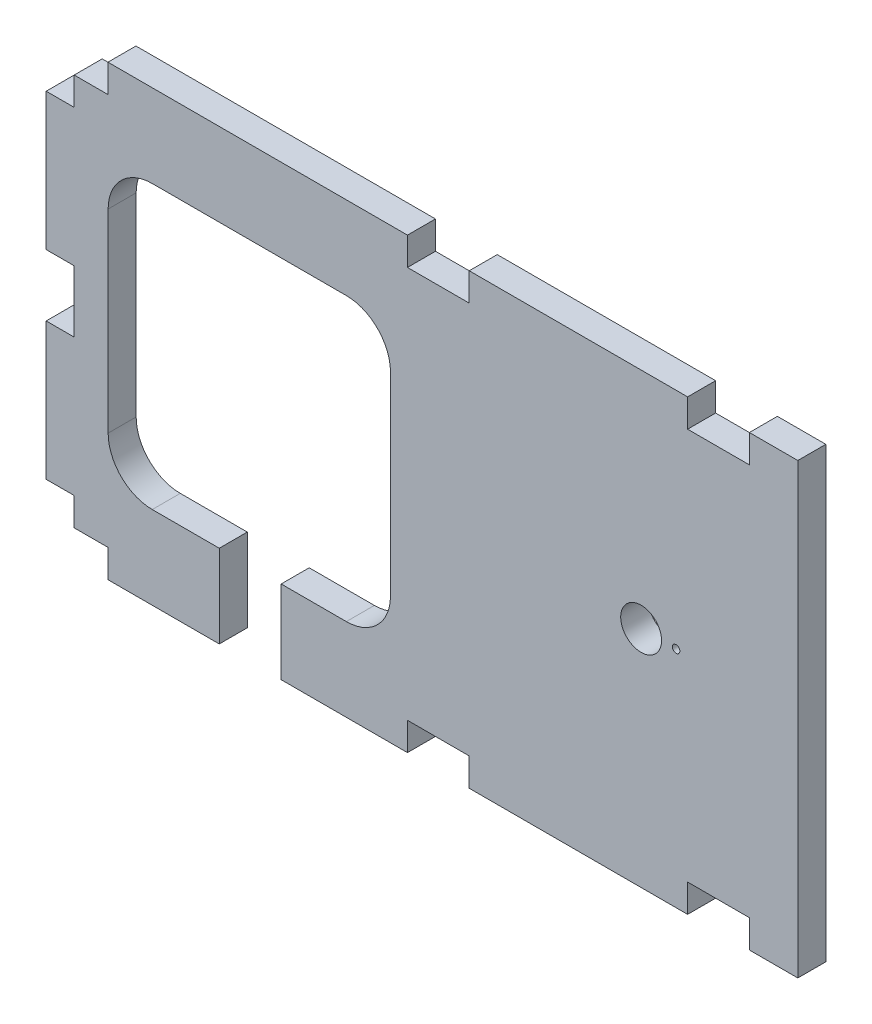
SolidWorks part; units mm, degrees
ref_plane "Front Plane" through (0, 0, 0) normal (0, 0, 1) x (1, 0, 0)
ref_plane "Top Plane" through (0, 0, 0) normal (0, 1, 0) x (1, 0, 0)
ref_plane "Right Plane" through (0, 0, 0) normal (1, 0, 0) x (0, 0, -1)
sketch "Sketch2" plane through (0, 0, 0) normal (0, 0, 1) x (1, 0, 0)
  line L1 (-88.9, -50.8) -> (88.9, -50.8)
  line L2 (-88.9, -50.8) -> (-88.9, 50.8)
  line L3 (-88.9, 50.8) -> (88.9, 50.8)
  line L4 (88.9, -50.8) -> (88.9, 50.8)
  line L5 (-88.9, -50.8) -> (88.9, 50.8) construction
  line L6 (-88.9, 50.8) -> (88.9, -50.8) construction
  point P0 (0, 0)
  dimension "D1" = 101.6
  dimension "D2" = 177.8
extrude "Boss-Extrude3" add sketch "Sketch2" along normal blind 6.35
sketch "Sketch3" plane through (0, 0, 6.35) normal (0, 0, 1) x (1, 0, 0)
  line L0 (-88.9, 0) -> (0, 0) construction
  line L1 (-88.9, 50.8) -> (-88.9, -50.8) construction
  line L2 (0, 0) -> (88.9, 0) construction
  line L3 (88.9, -50.8) -> (88.9, 50.8) construction
  line L4 (0, 50.8) -> (0, -50.8) construction
  line L5 (88.9, 50.8) -> (-88.9, 50.8) construction
  line L6 (-88.9, -50.8) -> (88.9, -50.8) construction
  line L7 (-9.4121, 0) -> (-42.6438, 0) construction
  line L8 (45.9739, 0) -> (-9.4121, 0) construction
  line L9 (-10.8508, 32) -> (-10.8508, 0)
  line L10 (-10.8508, -32) -> (-74.8508, -32)
  line L11 (-74.8508, -32) -> (-74.8508, 32)
  line L12 (-74.8508, 32) -> (-42.8508, 32)
  line L13 (-49.6596, -32) -> (-49.6596, -50.8)
  line L14 (-10.8508, 0) -> (-10.8508, -32)
  line L15 (-42.8508, 32) -> (-10.8508, 32)
  line L16 (-42.8508, 50.8) -> (-42.6438, 0) construction
  line L20 (-35.6279, -32) -> (-35.6279, -50.8)
  line L26 (-35.6279, -50.8) -> (-49.6596, -50.8)
  line L29 (26.7151, -50.8) -> (26.7151, 50.8) construction
  line L30 (-66.2169, 23.5732) -> (-66.2169, 28.0633) construction
  circle A7 centre (45.9739, 0) radius 4.635
  line M4 (-88.9, -50.8) -> (88.9, -50.8)
  dimension "D1" = 32
  dimension "D2" = 32
  dimension "D3" = 32
  dimension "D8" = 9.27
  dimension "D5" = 55.386
extrude "Cut-Extrude1" cut sketch "Sketch3" against normal through all contours L10 | L11 | L20 L10 L13 M4 | A7 region at (-42.8508, 0, 6.35) region at (-42.6438, -41.4, 6.35)
sketch "Sketch7" plane through (0, 0, 6.35) normal (0, 0, 1) x (1, 0, 0)
  line L1 (88.9, 50.8) -> (-88.9, 50.8) construction
  line L2 (-88.9, 50.8) -> (-88.9, -50.8) construction
  line L3 (-88.9, 50.8) -> (-88.9, -50.8) construction
  line L4 (-88.9, -7) -> (-88.9, 7)
  line L5 (-88.9, 50.8) -> (-74.9, 50.8)
  line L6 (-88.9, 50.8) -> (-88.9, 44.45)
  line L7 (-74.9, 44.45) -> (-82.55, 44.45)
  line L8 (-74.9, 50.8) -> (-74.9, 44.45)
  line L9 (-88.9, -50.8) -> (-74.9, -50.8)
  line L10 (-88.9, -50.8) -> (-88.9, -44.45)
  line L11 (-74.9, -44.45) -> (-82.55, -44.45)
  line L12 (-74.9, -50.8) -> (-74.9, -44.45)
  line L13 (-88.9, -7) -> (-82.55, -7)
  line L14 (-88.9, 7) -> (-82.55, 7)
  line L15 (-82.55, -7) -> (-82.55, 7)
  line L16 (88.9, -50.8) -> (88.9, 50.8) construction
  line L17 (7, 44.45) -> (-88.9, 44.45)
  line L18 (7, 44.45) -> (7, 50.8)
  line L19 (-7, 50.8) -> (7, 50.8)
  line L20 (-88.9, 44.45) -> (-88.9, 50.8)
  line L21 (70.509, 50.8) -> (70.509, 44.45)
  line L22 (-7, -32) -> (-7, 50.8) construction
  line L23 (7, -50.8) -> (56.509, -50.8)
  line L24 (56.509, -50.8) -> (70.509, -50.8)
  line L25 (56.509, -50.8) -> (56.509, -44.45)
  line L26 (56.509, -44.45) -> (70.509, -44.45)
  line L27 (70.509, -50.8) -> (70.509, -44.45)
  line L28 (56.509, 44.45) -> (70.509, 44.45)
  line L29 (56.509, 50.8) -> (56.509, 44.45)
  line L30 (56.509, 50.8) -> (70.509, 50.8)
  line L31 (7, 50.8) -> (56.509, 50.8)
  line L32 (-10.8508, -32) -> (-35.6279, -32) construction
  line L33 (-88.9, -50.8) -> (-49.6596, -50.8) construction
  line L34 (-88.9, -44.45) -> (-82.55, -44.45)
  line L35 (7, -50.8) -> (7, -44.45)
  line L36 (-74.9, -44.45) -> (-69.2798, -44.45)
  line L37 (7, -44.45) -> (-7, -44.45)
  line L38 (-88.9, -7) -> (-88.9, -44.45) construction
  line L39 (-7, 44.45) -> (-7, 50.8)
  line L40 (-88.9, -7) -> (-82.55, 7) construction
  line L41 (-7, 50.8) -> (7, 50.8)
  line L42 (-7, -44.45) -> (-7, -50.8)
  line L43 (0, 0) -> (-88.9, 0) construction
  line L44 (-82.55, -7) -> (-88.9, 7) construction
  line L45 (-7, -50.8) -> (7, -50.8)
  line L46 (-88.9, 0) -> (88.9, 0) construction
  line L47 (-69.2798, 50.8) -> (-69.2798, -50.8) construction
  line L48 (-69.2798, 50.8) -> (-40.95, 44.45) construction
  line L49 (-69.2798, -44.45) -> (-69.2798, -50.8) construction
  line L50 (-82.55, 44.45) -> (-82.55, 38.1)
  line L51 (-82.55, 38.1) -> (-88.9, 38.1)
  line L52 (-88.9, 44.45) -> (-88.9, 38.1)
  line L54 (-82.55, -44.45) -> (-82.55, -38.1)
  line L55 (-82.55, -38.1) -> (-88.9, -38.1)
  line L56 (-88.9, -44.45) -> (-88.9, -38.1)
  line M9 (88.9, 50.8) -> (-88.9, 50.8)
  line M10 (-88.9, 50.8) -> (-88.9, -50.8)
  line M11 (-88.9, -50.8) -> (-49.6596, -50.8)
  line M97 (-35.6279, -50.8) -> (88.9, -50.8)
  dimension "D5" = 6.35
  dimension "D6" = 6.35
  dimension "D7" = 6.35
  dimension "D8" = 49.509
  dimension "D9" = 18.391
extrude "Cut-Extrude2" cut sketch "Sketch7" against normal through all contours L27 L26 L25 M11 | L29 L28 L21 M9 | L54 L55 L12 L11 M10 M11 | L13 L15 L14 M10 | L51 L50 L7 L8 M9 M10 | L20 L17 L18 M9 | L37 L42 L35 M97 | L51 L50 L17 M10 | L54 L55 L34 M10 region at (63.509, 47.625, 6.35) region at (-85.725, 41.275, 6.35) region at (-85.725, 0, 6.35) region at (-85.725, -41.275, 6.35) region at (-81.9, -47.625, 6.35) region at (-81.9, 47.625, 6.35) region at (0, 47.625, 6.35) region at (63.509, -47.625, 6.35) region at (0, -47.625, 6.35)
sketch "Sketch8" plane through (0, 0, 6.35) normal (0, 0, 1) x (1, 0, 0)
  line L0 (45.9739, 0) -> (53.8987, 0) construction
  line L1 (81.4901, 50.8) -> (81.4901, -50.8)
  line L2 (88.9, 50.8) -> (70.509, 50.8) construction
  line L3 (81.4901, -50.8) -> (88.9, -50.8)
  line L4 (88.9, 50.8) -> (88.9, -50.8)
  line L5 (88.9, -50.8) -> (88.9, 50.8) construction
  line L6 (88.9, 50.8) -> (81.4901, 50.8)
  line L7 (70.509, -50.8) -> (88.9, -50.8) construction
  circle A1 centre (53.8987, 0) radius 0.8509
  dimension "D1" = 1.7018
extrude "Cut-Extrude3" cut sketch "Sketch8" against normal blind 10
fillet "Fillet4" radius 10 4 edges at (-10.8508, 32, 3.175) (-74.8508, 32, 3.175) (-10.8508, -32, 3.175) (-74.8508, -32, 3.175)
